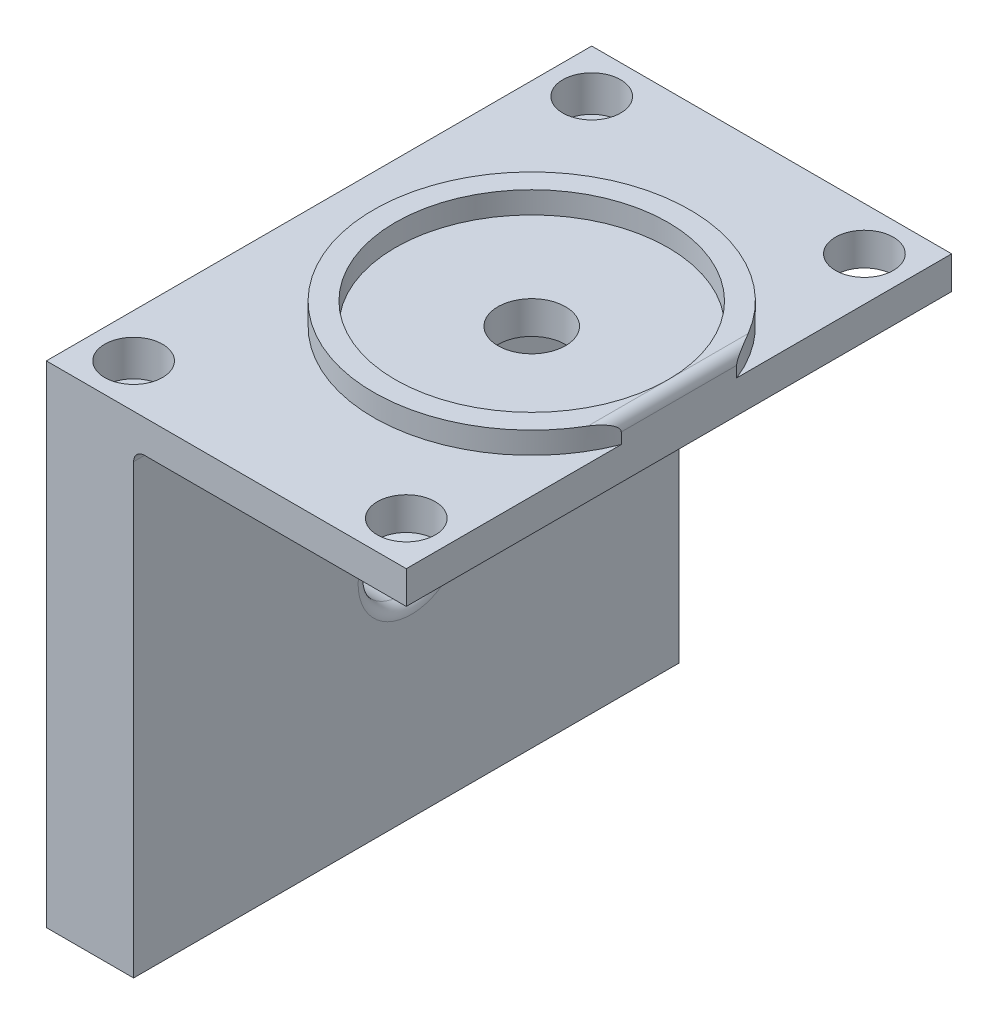
SolidWorks part; units mm, degrees
ref_plane "Front Plane" through (0, 0, 0) normal (0, 0, 1) x (1, 0, 0)
ref_plane "Top Plane" through (0, 0, 0) normal (0, 1, 0) x (1, 0, 0)
ref_plane "Right Plane" through (0, 0, 0) normal (1, 0, 0) x (0, 0, -1)
sketch "Sketch1" plane through (0, 0, 0) normal (0, 1, 0) x (1, 0, 0)
  line L1 (-10.223, 36.3848) -> (14.777, 36.3848)
  line L2 (-10.223, 36.3848) -> (-10.223, -13.6152)
  line L3 (-10.223, -13.6152) -> (14.777, -13.6152)
  line L4 (14.777, 36.3848) -> (14.777, -13.6152)
  circle A0 centre (1.277, 11.3848) radius 3.1
  dimension "D3" = 6.2
  dimension "D1" = 50
  dimension "D2" = 25
  dimension "D4" = 13.5
  dimension "D5" = 25
extrude "Boss-Extrude1" add sketch "Sketch1" along normal blind 3
sketch "Sketch2" plane through (-10.223, 0, 0) normal (-1, 0, 0) x (0, 0, 1)
  line L0 (55, 0) -> (-55, 0) construction
  line L1 (-36.3848, 3) -> (13.6152, 3)
  line L2 (-36.3848, 3) -> (-36.3848, 0)
  line L3 (-36.3848, 0) -> (13.6152, 0)
  line L4 (13.6152, 3) -> (13.6152, 0)
  line L5 (13.6152, 3) -> (13.6152, 0) construction
extrude "Boss-Extrude2" add sketch "Sketch2" along normal blind 8
sketch "Sketch3" plane through (0, 0, 0) normal (0, -1, 0) x (1, 0, 0)
  line L0 (-18.223, 13.6152) -> (14.777, 13.6152) construction
  line L1 (-18.223, -36.3848) -> (-10.223, -36.3848)
  line L2 (-18.223, -36.3848) -> (-18.223, 13.6152)
  line L3 (-18.223, 13.6152) -> (-10.223, 13.6152)
  line L4 (-10.223, -36.3848) -> (-10.223, 13.6152)
  dimension "D1" = 8
extrude "Boss-Extrude3" add sketch "Sketch3" along normal blind 42
sketch "Sketch4" plane through (0, 3, 0) normal (0, 1, 0) x (1, 0, 0)
  line L0 (-18.223, -13.6152) -> (-18.223, 36.3848) construction
  line L1 (14.777, 36.3848) -> (-18.223, 36.3848) construction
  line L2 (-18.223, -13.6152) -> (14.777, -13.6152) construction
  circle A0 centre (-14.223, 32.3848) radius 2.65
  circle A1 centre (-14.223, -9.6152) radius 2.65
  dimension "D2" = 5.3
  dimension "D4" = 5.3
  dimension "D5" = 4
  dimension "D6" = 4
  dimension "D1" = 4
  dimension "D3" = 4
extrude "Cut-Extrude1" cut sketch "Sketch4" against normal blind 3.3
ref_plane "Plane1" through (0, -19.5, 0) normal (0, 1, 0) x (1, 0, 0)
mirror "Mirror1" about plane through (0, -19.5, 0) normal (0, 1, 0) of "Cut-Extrude1"
sketch "Sketch5" plane through (-18.223, 0, 0) normal (-1, 0, 0) x (0, 0, 1)
  line L0 (18.15, 0) -> (-18.15, 0) construction
  line L1 (-8.6015, -23.1212) -> (-8.3819, -19.2592) construction
  line L2 (-8.3819, -19.2592) -> (-11.6167, -17.138) construction
  line L3 (-11.6167, -17.138) -> (-15.0711, -18.8788) construction
  line L4 (-15.0711, -18.8788) -> (-15.2907, -22.7408) construction
  line L5 (-15.2907, -22.7408) -> (-12.0559, -24.862) construction
  line L6 (-12.0559, -24.862) -> (-8.6015, -23.1212) construction
  circle A0 centre (-11.8363, -21) radius 3.35 construction
  circle A1 centre (-11.8363, -21) radius 3.8682
  dimension "D1" = 21
  dimension "D2" = 6.7
extrude "Cut-Extrude2" cut sketch "Sketch5" against normal blind 9
fillet "Fillet2" radius 1 1 edges at (-10.223, -21, -7.968)
ref_plane "Plane2" through (-1.723, 0, 0) normal (-1, 0, 0) x (0, 0, 1)
mirror "Mirror2" about plane through (-1.723, 0, 0) normal (-1, 0, 0) of "Cut-Extrude1"
sketch "Sketch6" plane through (0, 3, 0) normal (0, 1, 0) x (1, 0, 0)
  line L0 (1.277, 14.4848) -> (1.277, 8.2848) construction
  line L1 (14.777, -13.6152) -> (14.777, 36.3848) construction
  line L2 (14.777, 16.6763) -> (14.777, 6.0933)
  circle A0 centre (1.277, 11.3848) radius 3.1 construction
  circle A1 centre (1.277, 11.3848) radius 3.1
  circle A2 centre (1.277, 11.3848) radius 12.5
  arc A3 (14.777, 16.6763) -> (14.777, 6.0933) centre (1.277, 11.3848) ccw
  line M9 (14.777, -13.6152) -> (14.777, 36.3848)
  dimension "D1" = 25
  dimension "D2" = 2
extrude "Boss-Extrude4" add sketch "Sketch6" along normal blind 2 contours A3 A2 M9
fillet "Fillet3" radius 1 1 edges at (-10.223, 0, -11.3848)
fillet "Fillet4" radius 1 1 edges at (14.777, 5, -11.3848)
